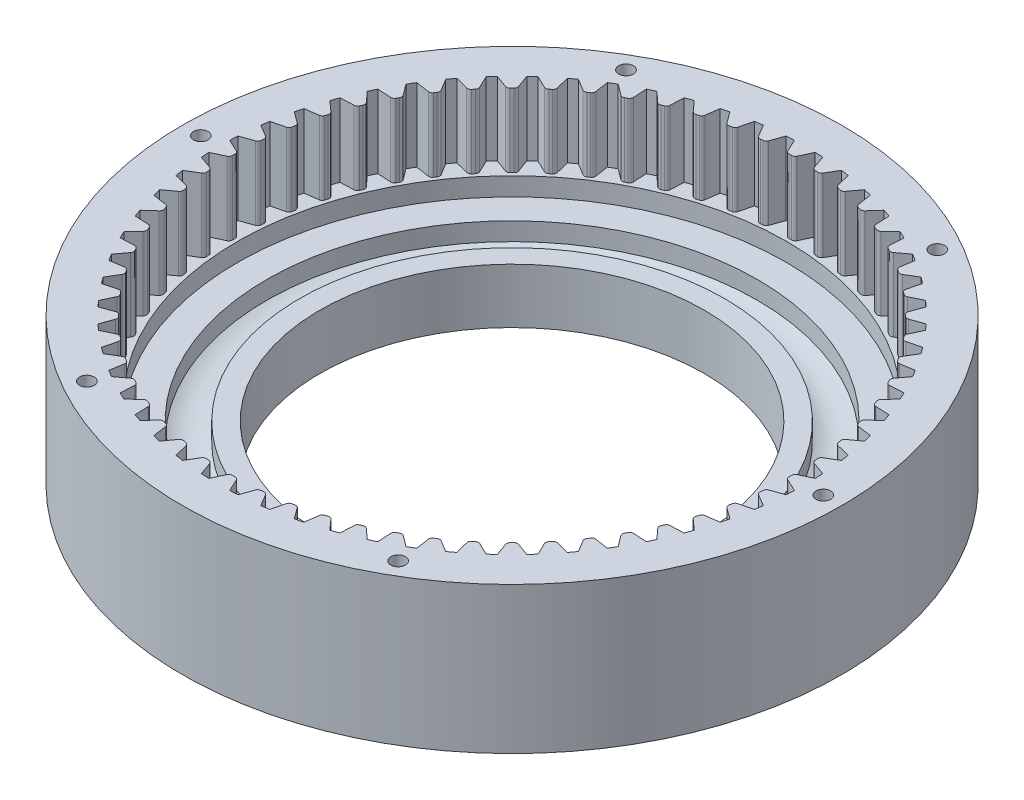
SolidWorks part; units mm, degrees
ref_plane "Front Plane" through (0, 0, 0) normal (0, 0, 1) x (1, 0, 0)
ref_plane "Top Plane" through (0, 0, 0) normal (0, 1, 0) x (1, 0, 0)
ref_plane "Right Plane" through (0, 0, 0) normal (1, 0, 0) x (0, 0, -1)
sketch "Sketch1" plane through (0, 0, 0) normal (0, 0, 1) x (1, 0, 0)
  line L0 (0, 0) -> (0, 36.773) construction
  line L2 (-90, 0) -> (-90, 40)
  line L3 (-90, 40) -> (-80, 40)
  line L4 (-80, 40) -> (-80, 20)
  line L5 (-75, 15) -> (-67, 15)
  line L6 (-67, 15) -> (-67, 10.0697)
  line L7 (-58, 10.0697) -> (-58, 15)
  line L8 (-58, 15) -> (-52.5, 15)
  line L10 (-67, 15) -> (-58, 15) construction
  line L12 (-52.5, 15) -> (-52.5, 0)
  line L16 (-52.5, 0) -> (-90, 0)
  line L18 (-80, 20) -> (-75, 20)
  line L19 (-75, 20) -> (-75, 15)
  arc A0 (-67, 10.0697) -> (-58, 10.0697) centre (-62.5, 19) ccw
  point P14 (-62.5, 15)
  point P16 (-62.5, 9)
  dimension "D5" = 10
  dimension "D2" = 150
  dimension "D3" = 40
  dimension "D4" = 9
  dimension "D6" = 6
  dimension "D7" = 160
  dimension "D8" = 15
  dimension "D9" = 105
  dimension "D12" = 20
  dimension "D13" = 180
  dimension "D14" = 125
revolve "Revolve1" add sketch "Sketch1" angle 360 about L0
sketch "Sketch2" plane through (0, 20, 0) normal (0, 1, 0) x (1, 0, 0)
  line L0 (-79.9495, 2.8417) -> (-76.5774, 1.2692)
  line L1 (-76.5774, -1.2692) -> (-79.9495, -2.8417)
  line L2 (-76, -0.3629) -> (-76, 0.3629)
  circle A1 centre (0, 0) radius 80 construction
  circle A2 centre (0, 0) radius 80 construction
  arc A4 (-79.9495, 2.8417) -> (-79.9495, -2.8417) centre (0, 0) ccw
  arc A5 (-76, -0.3629) -> (-76.5774, -1.2692) centre (-77, -0.3629) cw
  arc A6 (-76.5774, 1.2692) -> (-76, 0.3629) centre (-77, 0.3629) cw
  point P9 (-76, -1)
  point P11 (-80, 0)
  point P15 (-76, 1)
  dimension "D1" = 4
  dimension "D4" = 1
  dimension "D2" = 50
  dimension "D3" = 2
extrude "Boss-Extrude1" add sketch "Sketch2" along normal up to surface (20 mm away) up to face at (0, 40, -90)
pattern_circular "CirPattern1" count 64 over 360 about axis through (0, 0, 0) along (0, -1, 0) of "Boss-Extrude1" reverse direction yes
sketch "Sketch3" plane through (0, 40, 0) normal (0, 1, 0) x (1, 0, 0)
  circle A0 centre (-85, 0) radius 2
  dimension "D2" = 4
  dimension "D1" = 85
extrude "Cut-Extrude1" cut sketch "Sketch3" against normal blind 15
pattern_circular "CirPattern2" count 6 over 360 about axis through (0, 0, 0) along (0, -1, 0) of "Cut-Extrude1" reverse direction yes
sketch "Sketch4" plane through (0, 0, 0) normal (0, -1, 0) x (-1, 0, 0)
  circle A0 centre (78, 0) radius 4
  dimension "D1" = 8
  dimension "D2" = 78
extrude "Cut-Extrude2" cut sketch "Sketch4" against normal blind 12
pattern_circular "CirPattern3" count 4 over 360 about axis through (0, 0, 0) along (0, -1, 0) of "Cut-Extrude2" reverse direction yes
